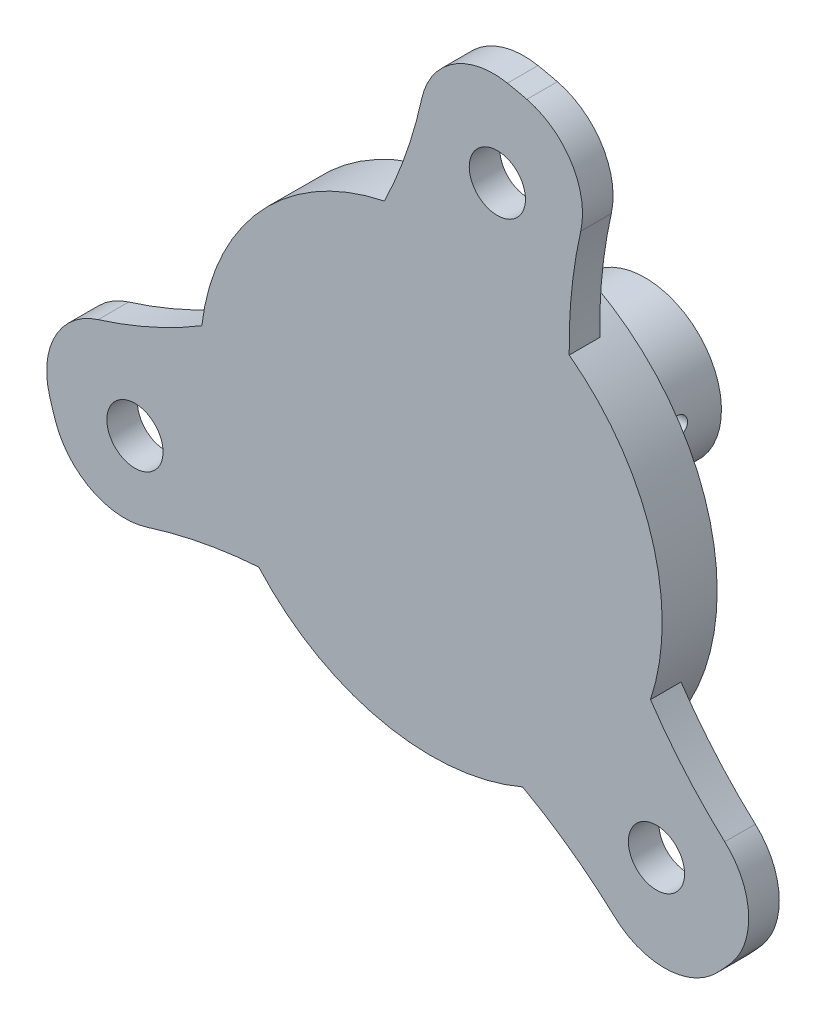
SolidWorks part; units mm, degrees
ref_plane "Front Plane" through (0, 0, 0) normal (0, 0, 1) x (1, 0, 0)
ref_plane "Top Plane" through (0, 0, 0) normal (0, 1, 0) x (1, 0, 0)
ref_plane "Right Plane" through (0, 0, 0) normal (1, 0, 0) x (0, 0, -1)
sketch "Sketch1" plane through (0, 0, 0) normal (0, 0, 1) x (1, 0, 0)
  circle A0 centre (0, 0) radius 65
  dimension "D1" = 130
extrude "Boss-Extrude1" add sketch "Sketch1" along normal blind 5
sketch "Sketch2" plane through (0, 0, 5) normal (0, 0, 1) x (1, 0, 0)
  line L1 (12.5, -7.2169) -> (12.5, 7.2169)
  line L2 (12.5, 7.2169) -> (0, 14.4338)
  line L3 (0, 14.4338) -> (-12.5, 7.2169)
  line L4 (-12.5, 7.2169) -> (-12.5, -7.2169)
  line L5 (-12.5, -7.2169) -> (0, -14.4338)
  line L6 (0, -14.4338) -> (12.5, -7.2169)
  circle A0 centre (0, 0) radius 12.5 construction
  dimension "D1" = 25
extrude "Boss-Extrude2" [suppressed] add sketch "Sketch2" along normal blind 5
sketch "Sketch3" [suppressed] plane through (0, 0, 10) normal (0, 0, 1) x (1, 0, 0)
  circle A0 centre (0, 0) radius 10
  dimension "D1" = 20
extrude "Boss-Extrude3" [suppressed] add sketch "Sketch3" along normal blind 25
fillet "Fillet1" [suppressed] radius 3
sketch "Sketch4" [suppressed] plane through (0, 0, 35) normal (0, 0, 1) x (1, 0, 0)
  circle A0 centre (0, 0) radius 4.95
  dimension "D1" = 9.9
extrude "Cut-Extrude1" [suppressed] cut sketch "Sketch4" against normal through all
hole_wizard "Ø1.0mm Dowel Hole1" [suppressed] positions "3DSketch1" profile "Sketch5" hole size "Ø1.0" standard "ANSI Metric"
sketch3d "3DSketch1" [suppressed]
  point P0 (-8.696, 4.9375, 25.8574)
  point P2 (4.8442, 8.7483, 25.3286)
sketch "Sketch5" plane through (-8.696, 4.9375, 25.8574) normal (0, 0, 1) x (-0.4938, -0.8696, 0)
  line L0 (0, 0) -> (0, 34)
  line L1 (0, 34) -> (1.4, 33.1588)
  line L2 (1.4, 33.1588) -> (1.4, 0)
  line L5 (1.4, 0) -> (0, 0)
  line L10 (0, 34) -> (-1.4, 33.1588) construction
  line L11 (0, -6.35) -> (0, 107.95) construction
  dimension "Hole Dia." = 2.8
  dimension "Hole Depth" = 34
  dimension "Drill Angle" = 118
sketch "Sketch6" plane through (0, 0, 5) normal (0, 0, 1) x (1, 0, 0)
  line L0 (0, 65) -> (0, 0) construction
  line L1 (0, 0) -> (-64.7527, -5.6651) construction
  arc A3 (-64.7527, -5.6651) -> (0, 65) centre (-77.7496, 71.2444) ccw
  circle A4 centre (0, 0) radius 65 construction
  arc A5 (27.4702, 58.91) -> (56.2917, -32.5) centre (100.5743, 31.711) ccw
  arc A6 (37.2825, -53.2449) -> (-56.2917, -32.5) centre (-22.8247, -102.9554) ccw
  circle A8 centre (0, 0) radius 65
  circle A9 centre (0, 0) radius 65
  point P8 (100.8796, 48.3276)
  point P9 (0, 0)
  point P15 (0, 0)
  point P16 (0, 0)
  dimension "D1" = 95
  dimension "D3" = 3
  dimension "D2" = 78
  dimension "D4" = 0
extrude "Cut-Extrude2" cut sketch "Sketch6" against normal blind 25
fillet "Fillet2" radius 12 6 edges at (37.2825, -53.2449, 2.5) (-56.2917, -32.5, 2.5) (27.4702, 58.91, 2.5) (56.2917, -32.5, 2.5) (-64.7527, -5.6651, 2.5) (0, 65, 2.5)
sketch "Sketch7" plane through (0, 0, 0) normal (0, 0, -1) x (-1, 0, 0)
  line L0 (-14.0686, 63.4592) -> (0, 0) construction
  arc A1 (-12.4751, 63.7916) -> (-15.6532, 63.0871) centre (0, 0) ccw construction
  point P0 (-16.0165, 72.2459)
  point P1 (-17.3152, 78.1037)
  point P10 (72.2459, 16.0165)
  point P11 (16.0165, -72.2459)
  point P12 (-72.2459, -16.0165)
  point P13 (0, 0)
  dimension "D2" = 4
sketch "Sketch9" plane through (0, 0, 0) normal (0, 0, -1) x (-1, 0, 0)
  circle A0 centre (0, 0) radius 12.5
  dimension "D1" = 25
extrude "Boss-Extrude4" add sketch "Sketch9" along normal blind 30
fillet "Fillet3" [suppressed] radius 15
sketch "Sketch10" plane through (0, 0, -30) normal (0, 0, -1) x (-1, 0, 0)
  circle A0 centre (0, 0) radius 4.95
  dimension "D1" = 9.9
extrude "Cut-Extrude3" cut sketch "Sketch10" against normal through all
sketch "Sketch11" plane through (0, 0, -30) normal (0, 0, -1) x (-1, 0, 0)
  line L1 (-2.5, 2.45) -> (2.5, 2.45)
  line L2 (-2.5, 2.45) -> (-2.5, 7.45)
  line L3 (-2.5, 7.45) -> (2.5, 7.45)
  line L4 (2.5, 2.45) -> (2.5, 7.45)
  line L5 (-2.5, 2.45) -> (2.5, 7.45) construction
  line L6 (-2.5, 7.45) -> (2.5, 2.45) construction
  circle A0 centre (0, 0) radius 4.95 construction
  point P0 (0, 4.95)
  point P7 (0, 0)
  dimension "D1" = 5
  dimension "D2" = 5
extrude "Cut-Extrude4" cut sketch "Sketch11" against normal through all
hole_wizard "Ø1.0mm Dowel Hole3" positions "3DSketch3" profile "Sketch12" hole size "Ø1.0" standard "ANSI Metric"
sketch3d "3DSketch3"
  point P0 (8.5996, 9.0717, -22.4664)
  point P1 (12.4474, 1.1452, -23.0939)
  point P3 (0, -12.5, -18.5782)
  point P7 (0, 0, -14.3952)
  point P10 (1.4675, -12.4136, -18.613)
  point P11 (0, 0, 0)
  point P12 (-0.0372, -12.4999, -18.5782)
sketch "Sketch12" plane through (0, -12.5, -18.5782) normal (1, 0, 0) x (0, 0, -1)
  line L0 (0, 0) -> (0, 34)
  line L1 (0, 34) -> (1.4, 33.1588)
  line L2 (1.4, 33.1588) -> (1.4, 0)
  line L5 (1.4, 0) -> (0, 0)
  line L10 (0, 34) -> (-1.4, 33.1588) construction
  line L11 (0, -6.35) -> (0, 107.95) construction
  dimension "Hole Dia." = 2.8
  dimension "Hole Depth" = 34
  dimension "Drill Angle" = 118
sketch "Sketch13" plane through (0, 0, 0) normal (0, 0, -1) x (-1, 0, 0)
  circle A0 centre (0, 0) radius 37.8
  dimension "D1" = 75.6
extrude "Boss-Extrude5" add sketch "Sketch13" along normal blind 4 and the other way up to surface (5 mm away) other way up to face at (0, 3.5556, 5)
sketch "Sketch15" plane through (0, 0, 0) normal (0, 0, -1) x (-1, 0, 0)
  line L0 (-14.0686, 63.4592) -> (0, 0) construction
  point P0 (-10.822, 48.8148)
  point P1 (47.6858, -15.0353)
  point P8 (-36.8639, -33.7795)
  point P9 (0, 0)
  dimension "D1" = 50
  dimension "D2" = 3
hole_wizard "Ø1.0mm Dowel Hole4" positions "3DSketch4" profile "Sketch16" hole size "Ø1.0" standard "ANSI Metric"
sketch3d "3DSketch4"
  point P0 (10.822, 48.8148, 0)
  point P3 (-48.4881, -16.6622, 0)
  point P5 (36.8639, -33.7795, 0)
sketch "Sketch16" plane through (10.822, 48.8148, 0) normal (1, 0, 0) x (0, 1, 0)
  line L0 (0, 0) -> (0, 34)
  line L1 (0, 34) -> (4.6, 31.236)
  line L2 (4.6, 31.236) -> (4.6, 0)
  line L5 (4.6, 0) -> (0, 0)
  line L10 (0, 34) -> (-4.6, 31.236) construction
  line L11 (0, -6.35) -> (0, 107.95) construction
  dimension "Hole Dia." = 9.2
  dimension "Hole Depth" = 34
  dimension "Drill Angle" = 118
fillet "Fillet4" radius 15 1 edges at (-12.5, 0, -4)
hole_wizard "Ø1.0mm Dowel Hole2" positions "3DSketch2" profile "Sketch8" hole size "Ø1.0" standard "ANSI Metric"
sketch3d "3DSketch2"
  point P0 (5.7432, 43.6236, 0)
  point P3 (-43.6236, 5.7432, 0)
  point P6 (-5.7432, -43.6236, 0)
  point P9 (43.6236, -5.7432, 0)
sketch "Sketch8" plane through (5.7432, 43.6236, 0) normal (1, 0, 0) x (0, 1, 0)
  line L0 (0, 0) -> (0, 34)
  line L1 (0, 34) -> (1.7, 32.9785)
  line L2 (1.7, 32.9785) -> (1.7, 0)
  line L5 (1.7, 0) -> (0, 0)
  line L10 (0, 34) -> (-1.7, 32.9785) construction
  line L11 (0, -6.35) -> (0, 107.95) construction
  dimension "Hole Dia." = 3.4
  dimension "Hole Depth" = 34
  dimension "Drill Angle" = 118
